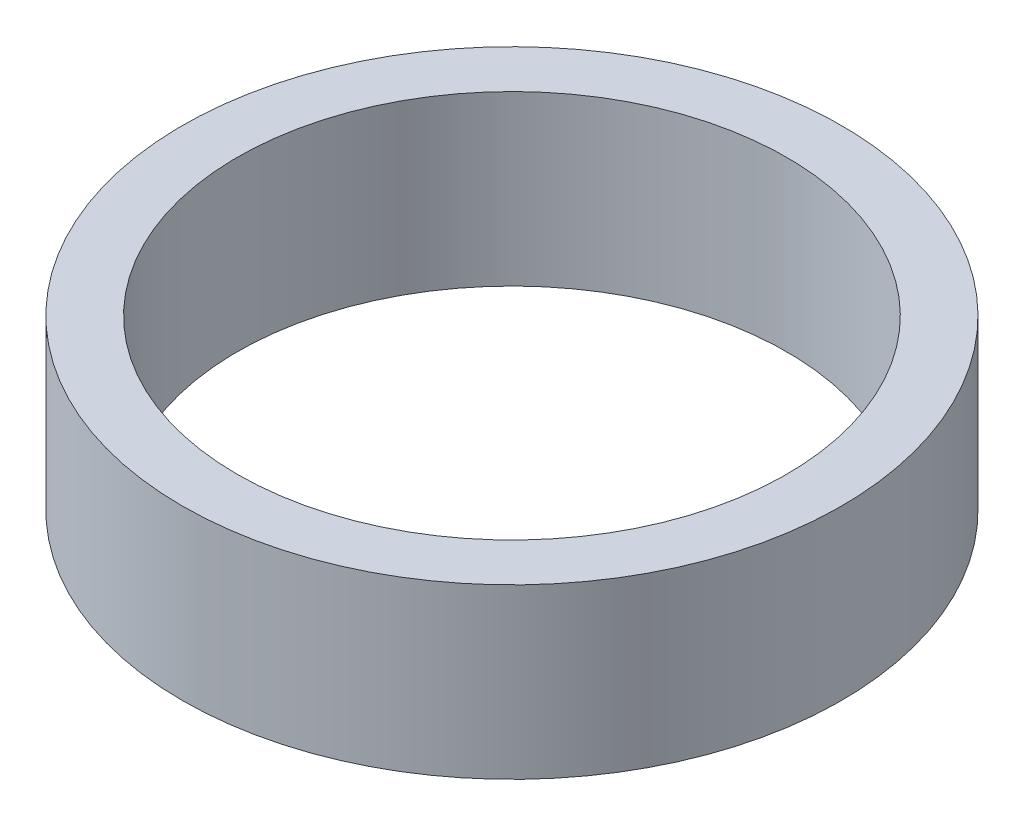
SolidWorks part; units mm, degrees
ref_plane "Front Plane" through (0, 0, 0) normal (0, 0, 1) x (1, 0, 0)
ref_plane "Top Plane" through (0, 0, 0) normal (0, 1, 0) x (1, 0, 0)
ref_plane "Right Plane" through (0, 0, 0) normal (1, 0, 0) x (0, 0, -1)
sketch "Sketch1" plane through (0, 0, 0) normal (0, 1, 0) x (1, 0, 0)
  circle A0 centre (0, 0) radius 45
  dimension "FLANGE_OD" = 90
extrude "Boss-Extrude1" add sketch "Sketch1" along normal blind 23
sketch "Sketch2" plane through (0, 0, 0) normal (0, 1, 0) x (1, 0, 0)
  circle A0 centre (0, 0) radius 37.5
  dimension "BORE_D" = 75
extrude "Cut-Extrude1" cut sketch "Sketch2" along normal through all
sketch "Sketch3" plane through (0, 23, 0) normal (0, 1, 0) x (1, 0, 0)
  circle A0 centre (0, 0) radius 20.4649 construction
  circle A1 centre (-20.4649, 0) radius 1.5
  dimension "BOLT_D" = 3
  dimension "BOLT_PCD" = 40.9297
extrude "Cut-Extrude2" cut sketch "Sketch3" against normal blind 13.9084 rebuild error yes
pattern_circular "CirPattern1" count 5 over 360 rebuild error yes
